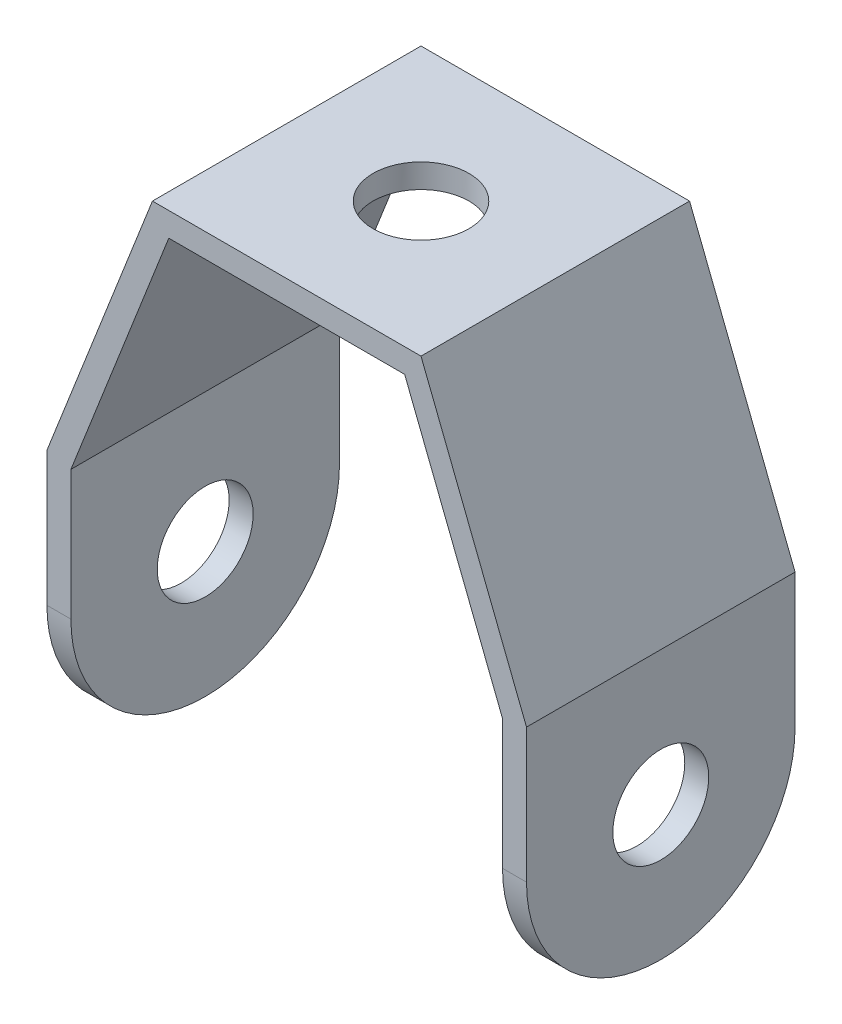
SolidWorks part; units mm, degrees
ref_plane "Plano frontal" through (0, 0, 0) normal (0, 0, 1) x (1, 0, 0)
ref_plane "Plano superior" through (0, 0, 0) normal (0, 1, 0) x (1, 0, 0)
ref_plane "Plano direito" through (0, 0, 0) normal (1, 0, 0) x (0, 0, -1)
sketch "Esboço1" plane through (0, 0, 0) normal (0, 0, 1) x (1, 0, 0)
  line L1 (-25, 28) -> (25, 28)
  line L2 (-25, 28) -> (-25, -28)
  line L3 (-25, -28) -> (25, -28)
  line L4 (25, 28) -> (25, -28)
  line L5 (-25, 28) -> (25, -28) construction
  line L6 (-25, -28) -> (25, 28) construction
  point P0 (0, 0)
  dimension "D1" = 50
  dimension "D2" = 56
extrude "Ressalto-extrusão1" add sketch "Esboço1" along normal blind 28
sketch "Esboço2" plane through (0, 0, 0) normal (0, 0, 1) x (1, 0, 0)
  line L0 (-25, -28) -> (-22.5, -28)
  line L1 (-25, -28) -> (25, -28) construction
  line L2 (-25, 0) -> (-14, 28)
  line L3 (-25, 28) -> (-25, -28) construction
  line L4 (25, 28) -> (-25, 28) construction
  line L5 (14, 28) -> (-14, 28) construction
  line L6 (-14, 28) -> (-25, 28)
  line L7 (-25, 28) -> (-25, 0)
  line L8 (14, 28) -> (25, 0)
  line L9 (25, -28) -> (25, 28) construction
  line L10 (25, 0) -> (25, 28)
  line L11 (25, 28) -> (14, 28)
  dimension "D1" = 2.5
  dimension "D2" = 30.0832
  dimension "D3" = 30.0832
sketch "Esboço3" plane through (0, 0, 28) normal (0, 0, 1) x (1, 0, 0)
  line L1 (-25, 28) -> (-25, -28) construction
  line L2 (-25, -28) -> (-25, 0)
  line L3 (25, -28) -> (22.5, -28)
  line L4 (-25, -28) -> (25, -28) construction
  line L5 (25, -28) -> (25, 0)
  line L6 (25, -28) -> (25, 28) construction
  line L7 (25, 0) -> (8.8342, 28)
  line L8 (25, 28) -> (-25, 28) construction
  line L9 (-25, 0) -> (-8.8342, 28)
  point P0 (-24.5907, 500000)
  dimension "D2" = 28
  dimension "D3" = 2.5
sketch "Esboço4" plane through (0, 28, 0) normal (0, 1, 0) x (1, 0, 0)
  line L0 (25, -28) -> (25, 0) construction
  line L2 (-25, -28) -> (-8.8342, -28) construction
  line L3 (-14, -14) -> (-14, -28)
  line L4 (14, -14) -> (14, -28)
  line L5 (25, -28) -> (8.8342, -28) construction
  circle A0 centre (0, -14) radius 14
  point P13 (-27.4835, -500000)
  dimension "D1" = 28
  dimension "D2" = 25
sketch "Esboço5" plane through (0, 0, 28) normal (0, 0, 1) x (1, 0, 0)
  line L0 (-25, -28) -> (-25, 0)
  line L1 (-25, 28) -> (-25, -28) construction
  line L2 (0, 28) -> (-14, 28)
  line L3 (22.5, -28) -> (22.5, -0.4735)
  line L4 (12.2961, 25.5) -> (22.5, -0.4735)
  line L5 (-22.5, -28) -> (22.5, -28)
  line L6 (25, -28) -> (25, 0)
  line L7 (25, -28) -> (25, 28) construction
  line L8 (14, 28) -> (-14, 28) construction
  line L9 (-14, 28) -> (-25, 0)
  line L10 (0, 28) -> (14, 28)
  line L11 (14, 28) -> (25, 0)
  line L12 (0, 25.5) -> (12.2961, 25.5)
  line L13 (0, 25.5) -> (-12.2961, 25.5)
  line L14 (-12.2961, 25.5) -> (-22.5, -0.4735)
  line L15 (-22.5, -28) -> (-22.5, -0.4735)
  line M12 (-25, -28) -> (25, -28)
  dimension "D1" = 2.5
  dimension "D2" = 30.0832
  dimension "D3" = 30.0832
extrude "Corte-extrusão1" cut sketch "Esboço5" against normal blind 28 contours L15 L3 L4 L12 L13 L14 M12 | L14 L15 L5 L3 L4 L12 L13 region at (0, -3.4881, 28)
extrude "Corte-extrusão7" cut sketch "Esboço2" against normal blind 28 and the other way blind 28 contours L6 L7 L2 | L10 L11 L8 region at (-21.3333, 18.6667, 0) region at (21.3333, 18.6667, 0)
sketch "Esboço6" plane through (0, 28, 0) normal (0, 1, 0) x (1, 0, 0)
  circle A0 centre (0, -14) radius 5
  point P3 (-114.1082, -21.5877)
  dimension "D1" = 10
sketch "Esboço7" plane through (-25, 0, 0) normal (-1, 0, 0) x (0, 0, 1)
  line L0 (28, -28) -> (0, -28) construction
  line L2 (28, 0) -> (28, -28) construction
  circle A0 centre (14, -14) radius 5
  dimension "D1" = 10
  dimension "D2" = 14
  dimension "D3" = 14
extrude "Corte-extrusão8" cut sketch "Esboço7" against normal through all
sketch "Esboço8" plane through (0, 28, 0) normal (0, 1, 0) x (1, 0, 0)
  circle A0 centre (0, -14) radius 5
  dimension "D1" = 10
extrude "Corte-extrusão9" cut sketch "Esboço8" against normal through all
fillet "Filete7" radius 14 2 edges at (-23.75, -28, 0) (-23.75, -28, 28)
fillet "Filete8" radius 14 2 edges at (23.75, -28, 28) (23.75, -28, 0)
